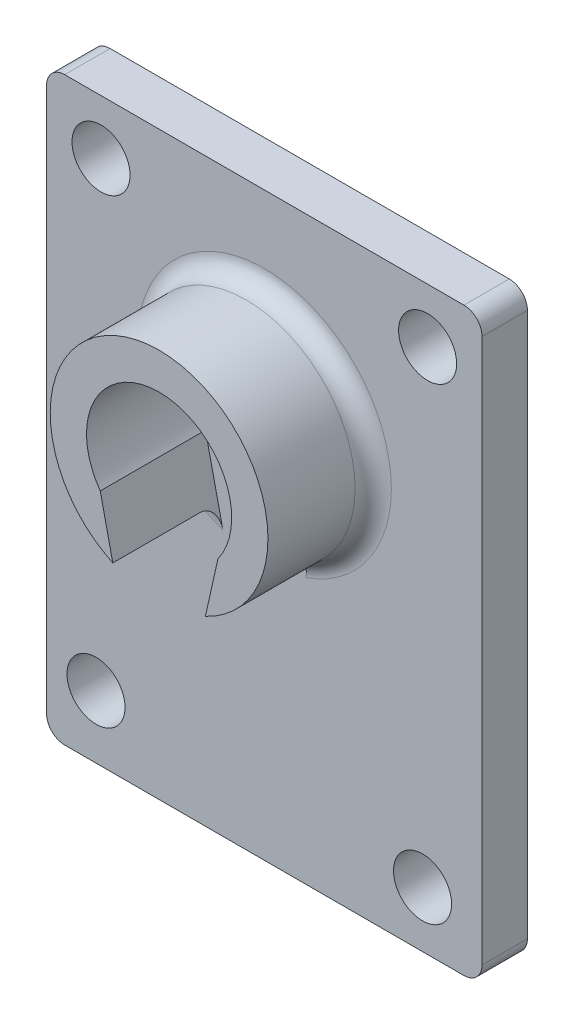
SolidWorks part; units mm, degrees
other "Marcação1"
sketch "Esboço4" plane through (-1.4022, -20.9776, 8.3) normal (-0.1528, -0.0621, 0.9863) x (0.9879, 0.0164, 0.1541)
ref_plane "Plano frontal" through (0, 0, 0) normal (0, 0, 1) x (1, 0, 0)
ref_plane "Plano superior" through (0, 0, 0) normal (0, 1, 0) x (1, 0, 0)
ref_plane "Plano direito" through (0, 0, 0) normal (1, 0, 0) x (0, 0, -1)
other "Centro da massa"
sketch "Esboço1" plane through (0, 0, 0) normal (0, 0, 1) x (1, 0, 0)
  line L0 (10.5978, 11.0224) -> (10.5978, -20.9776) construction
  line L1 (-1.4022, 11.0224) -> (22.5978, 11.0224)
  line L2 (-1.4022, 11.0224) -> (-1.4022, -20.9776)
  line L3 (-1.4022, -20.9776) -> (22.5978, -20.9776)
  line L4 (22.5978, 11.0224) -> (22.5978, -20.9776)
  line L5 (-1.4022, -4.7187) -> (22.5978, -4.9776) construction
  line L6 (-1.4022, -20.9776) -> (22.5978, 11.0224) construction
  circle A0 centre (1.5978, 8.0224) radius 1.6
  circle A1 centre (19.5978, 8.0224) radius 1.6
  circle A2 centre (19.318, -17.9098) radius 1.6
  circle A3 centre (1.3222, -17.5215) radius 1.6
  dimension "D3" = 3.2
  dimension "D1" = 24
  dimension "D2" = 32
  dimension "D4" = 3
  dimension "D5" = 3
extrude "Ressalto-extrusão1" add sketch "Esboço1" along normal blind 2.5
sketch "Esboço2" plane through (0, 0, 2.5) normal (0, 0, 1) x (1, 0, 0)
  line L0 (-1.4022, 6.2724) -> (22.5978, 6.2724) construction
  line L1 (-1.4022, 11.0224) -> (-1.4022, -20.9776) construction
  line L2 (22.5978, -20.9776) -> (22.5978, 11.0224) construction
  line L3 (22.5978, 11.0224) -> (-1.4022, 11.0224) construction
  line L4 (-1.4022, -8.2276) -> (22.5978, -8.2276) construction
  line L5 (16.5978, 11.0224) -> (16.5978, -20.9776) construction
  line L6 (-1.4022, -20.9776) -> (22.5978, -20.9776) construction
  line L7 (4.5978, 11.0224) -> (4.5978, -20.9776) construction
  line L8 (4.5978, -8.2276) -> (16.5978, -8.2276)
  line L9 (16.5978, -8.2276) -> (16.5978, 6.2724)
  line L10 (16.5978, 6.2724) -> (4.5978, 6.2724)
  line L11 (4.5978, 6.2724) -> (4.5978, -8.2276)
  line L12 (8.0478, -8.2276) -> (13.1478, -8.2276)
  line L13 (13.1478, -2.8094) -> (13.1478, -8.2276)
  line L14 (8.0478, -2.8094) -> (8.0478, -8.2276)
  circle A0 centre (10.5978, 0.2724) radius 6
  circle A1 centre (10.5978, 0.2724) radius 4
  point P23 (8.0478, -5.1587)
  point P24 (13.1478, -5.1587)
  dimension "D6" = 8
  dimension "D1" = 4.75
  dimension "D2" = 14.5
  dimension "D3" = 12
  dimension "D4" = 6
extrude "Ressalto-extrusão2" add sketch "Esboço2" along normal blind 5.8 contours A1 L13 A0 L14 region at (6.4723, 4.3979, 2.5)
sketch "Esboço3" plane through (0, 0, 8.3) normal (0, 0, 1) x (1, 0, 0)
  line L0 (10.5978, 6.2724) -> (10.5978, -5.7276) construction
  line L1 (13.1478, -5.1587) -> (13.8414, -2.0682)
  line L2 (13.1478, -5.1587) -> (13.1478, -2.8094)
  line L3 (8.0478, -5.1587) -> (8.0478, -2.8094)
  line L4 (8.0478, -5.1587) -> (7.3541, -2.0682)
  arc A0 (13.1478, -5.1587) -> (8.0478, -5.1587) centre (10.5978, 0.2724) ccw construction
  arc A1 (13.1478, -2.8094) -> (8.0478, -2.8094) centre (10.5978, 0.2724) ccw construction
  circle A2 centre (10.5978, 0.2724) radius 4
  arc A3 (13.1478, -2.8094) -> (8.0478, -2.8094) centre (10.5978, 0.2724) ccw construction
  arc M5 (8.0478, -2.8094) -> (13.1478, -2.8094) centre (10.5978, 0.2724) cw
  line M6 (13.1478, -2.8094) -> (13.1478, -5.1587)
  line M8 (8.0478, -5.1587) -> (8.0478, -2.8094)
extrude "Corte-extrusão1" cut sketch "Esboço3" against normal blind 5.8 contours L4 M8 M5 | L1 M6 M5 region at (13.3755, -3.3702, 8.3) region at (7.82, -3.3702, 8.3)
fillet "Filete1" radius 1 1 edges at (10.5978, 6.2724, 2.5)
fillet "Filete2" radius 1 4 edges at (-1.4022, 11.0224, 1.25) (-1.4022, -20.9776, 1.25) (22.5978, -20.9776, 1.25) (22.5978, 11.0224, 1.25)
